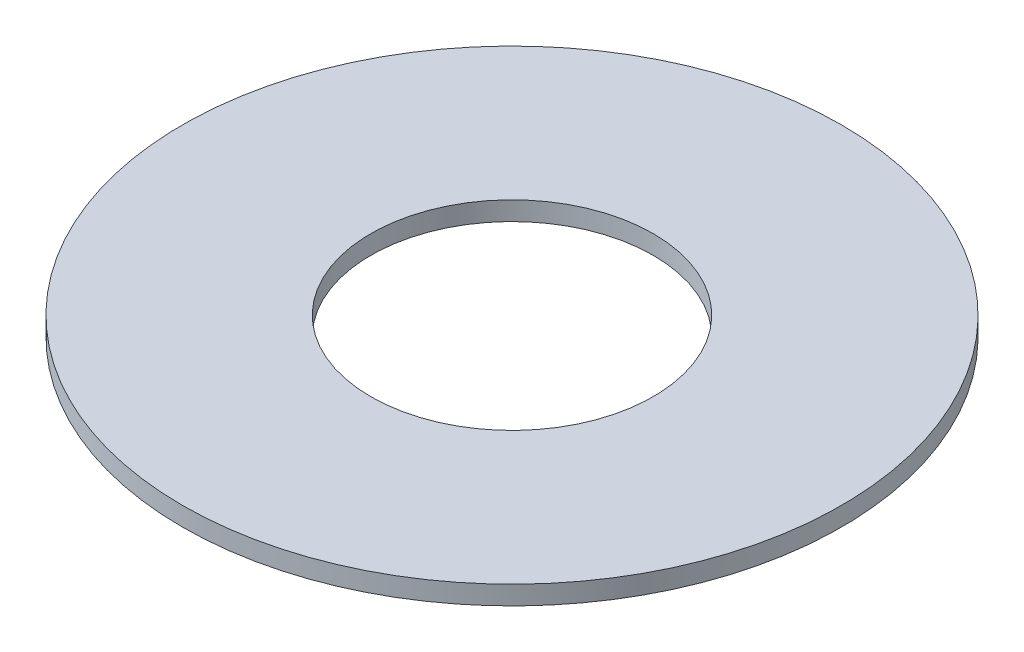
SolidWorks part; units mm, degrees
ref_plane "Front Plane" through (0, 0, 0) normal (0, 0, 1) x (1, 0, 0)
ref_plane "Top Plane" through (0, 0, 0) normal (0, 1, 0) x (1, 0, 0)
ref_plane "Right Plane" through (0, 0, 0) normal (1, 0, 0) x (0, 0, -1)
sketch "Sketch1" plane through (0, 0, 0) normal (0, 1, 0) x (1, 0, 0)
  circle A0 centre (0, 0) radius 87.5
  dimension "FLANGE_OD" = 175
extrude "Boss-Extrude1" add sketch "Sketch1" along normal blind 5
sketch "Sketch2" plane through (0, 0, 0) normal (0, 1, 0) x (1, 0, 0)
  circle A0 centre (0, 0) radius 37.5
  dimension "BORE_D" = 75
extrude "Cut-Extrude1" cut sketch "Sketch2" along normal through all
sketch "Sketch3" plane through (0, 5, 0) normal (0, 1, 0) x (1, 0, 0)
  circle A0 centre (0, 0) radius 31.3775 construction
  circle A1 centre (-31.3775, 0) radius 2.969
  dimension "BOLT_D" = 5.9379
  dimension "BOLT_PCD" = 62.7549
extrude "Cut-Extrude2" cut sketch "Sketch3" against normal blind 3.4415 rebuild error yes
pattern_circular "CirPattern1" count 6 over 360 rebuild error yes
